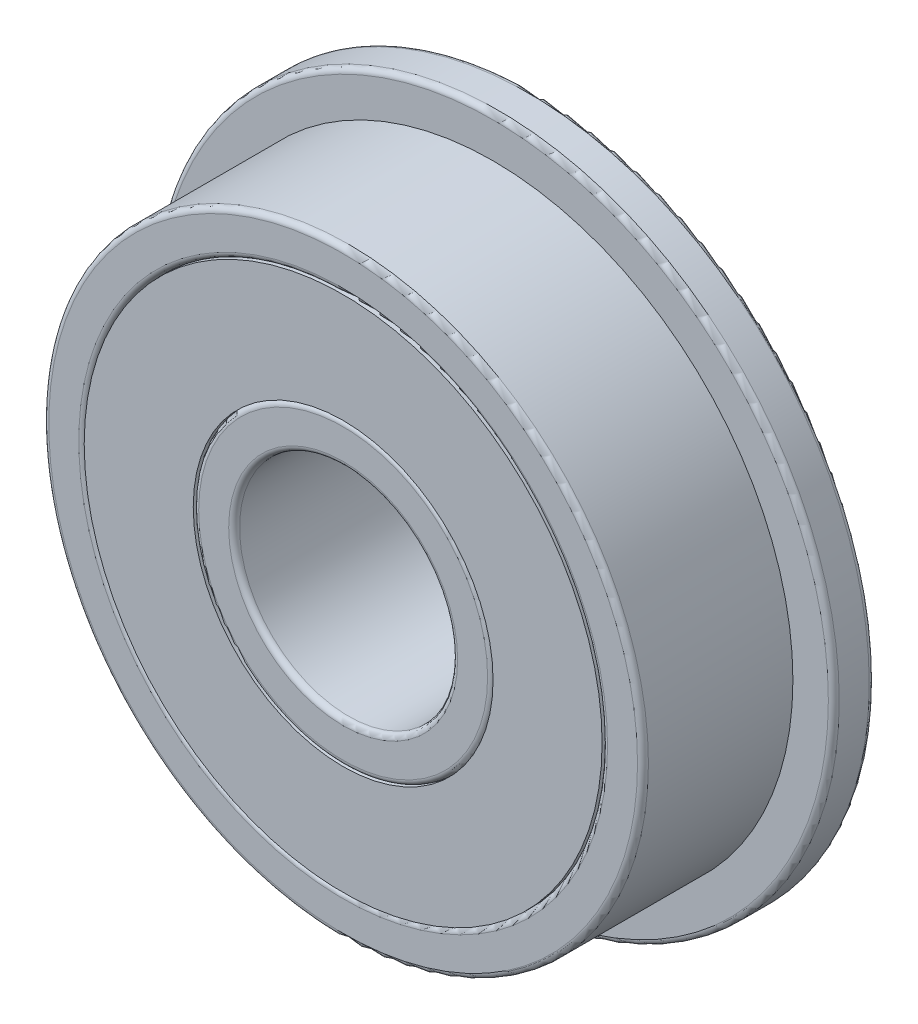
SolidWorks part; units mm, degrees
ref_plane "Front Plane" through (0, 0, 0) normal (0, 0, 1) x (1, 0, 0)
ref_plane "Top Plane" through (0, 0, 0) normal (0, 1, 0) x (1, 0, 0)
ref_plane "Right Plane" through (0, 0, 0) normal (1, 0, 0) x (0, 0, -1)
sketch "Sketch1" plane through (0, 0, 0) normal (0, 0, 1) x (1, 0, 0)
  circle A0 centre (0, 0) radius 11
  circle A1 centre (0, 0) radius 9.5
  circle A2 centre (0, 0) radius 4
  circle A3 centre (0, 0) radius 5.5
  dimension "D1" = 22
  dimension "D3" = 8
  dimension "D2" = 1.5
  dimension "D4" = 1.5
extrude "Boss-Extrude1" add sketch "Sketch1" along normal blind 7 contours A0 A1 | A3 A2 region at (-10.6889, 0, 0) region at (-5.3444, 0, 0)
fillet "Fillet2" radius 0.2 4 edges at (5.5, 0, 0) (4, 0, 0) (5.5, 0, 7) (4, 0, 7)
extrude "Boss-Extrude2" add sketch "Sketch1<3>" along normal blind 7 separate body contours A1 A3 region at (-9.2313, 0, 0)
sketch "Sketch1<3>" plane through (0, 0, 0) normal (0, 0, 1) x (1, 0, 0) same geometry as "Sketch1"
sketch "Sketch2" plane through (0, 0, 0) normal (0, 0, 1) x (1, 0, 0)
  circle A0 centre (0, 0) radius 12.5
  circle A1 centre (0, 0) radius 10.5
  dimension "D1" = 21
  dimension "D2" = 25
extrude "Boss-Extrude3" add sketch "Sketch2" along normal blind 1.5
fillet "Fillet1" radius 0.2 5 edges at (9.5, 0, 0) (11, 0, 7) (9.5, 0, 7) (12.5, 0, 0) (12.5, 0, 1.5)
equation "\"d-out\"= 22"
equation "\"d-in\"= 8"
equation "\"t\"= 1.5"
equation "\"b\"= 7"
equation "\"D1@Boss-Extrude2\"=\"b\""
equation "\"D1@Sketch1\"=\"d-out\""
equation "\"D3@Sketch1\"=\"d-in\""
equation "\"D4@Sketch1\"=\"t\""
equation "\"D2@Sketch1\"=\"t\""
equation "\"D1@Boss-Extrude1\"=\"b\""
equation "\"D1@Sketch2\"=\"d-out\"-1"
equation "\"df\"= 25'Diameter of Flange"
equation "\"D2@Sketch2\"=\"df\""
equation "\"bf\"= 1.5'Thickness of Flange"
